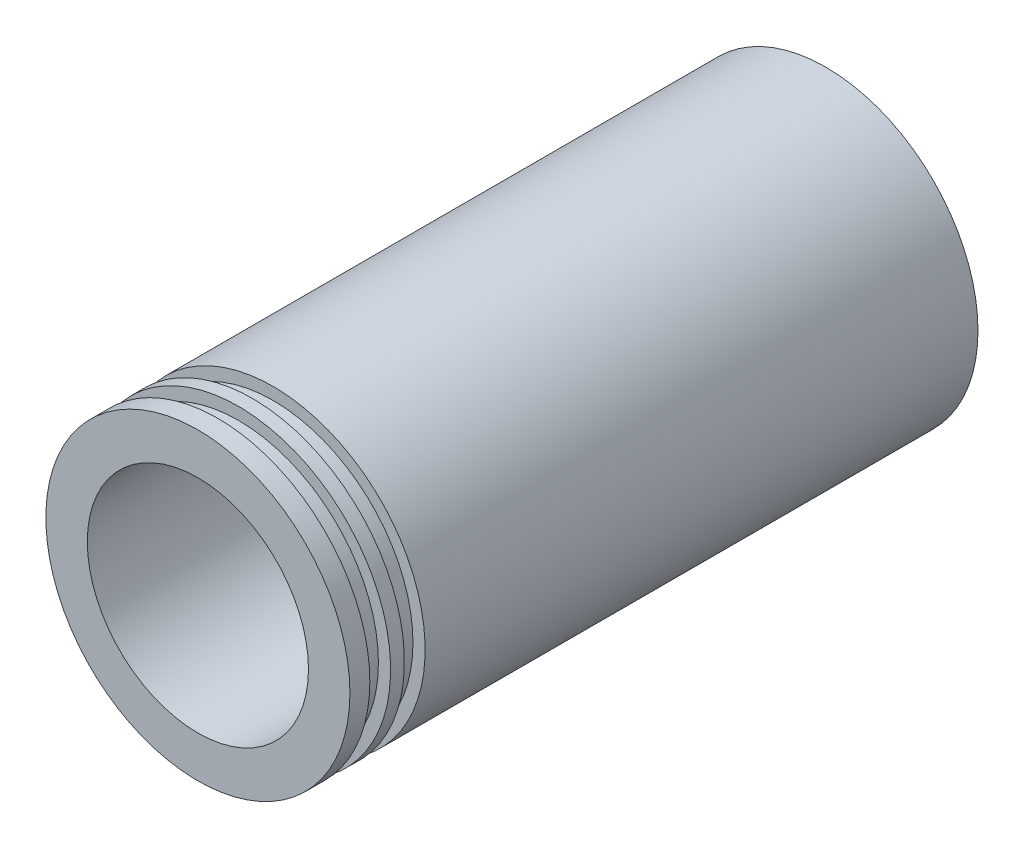
SolidWorks part; units mm, degrees
ref_plane "Front Plane" through (0, 0, 0) normal (0, 0, 1) x (1, 0, 0)
ref_plane "Top Plane" through (0, 0, 0) normal (0, 1, 0) x (1, 0, 0)
ref_plane "Right Plane" through (0, 0, 0) normal (1, 0, 0) x (0, 0, -1)
sketch "Sketch1" plane through (0, 0, 0) normal (0, 0, 1) x (1, 0, 0)
  circle A0 centre (0, 0) radius 34.925
  circle A1 centre (0, 0) radius 25.4
extrude "Boss-Extrude1" add sketch "Sketch1" along normal blind 144.272
sketch "Sketch2" plane through (0, 0, 0) normal (0, 1, 0) x (1, 0, 0)
  line L0 (25.4, 0) -> (-25.4, 0) construction
  circle A0 centre (0, -38.1) radius 5.588
  dimension "D1" = 38.1
extrude "Cut-Extrude1" cut sketch "Sketch2" against normal up to next
sketch "groove" plane through (0, 0, 0) normal (1, 0, 0) x (0, 0, -1)
  line L0 (-139.7, 34.925) -> (-139.7, 32.131)
  line L1 (-139.7, 32.131) -> (-134.9375, 32.131)
  line L2 (-134.9375, 32.131) -> (-134.9375, 34.925)
  line L3 (-134.9375, 34.925) -> (-131.7625, 34.925)
  line L4 (-131.7625, 34.925) -> (-131.7625, 32.131)
  line L5 (-131.7625, 32.131) -> (-127, 32.131)
  line L6 (-127, 32.131) -> (-127, 34.925)
  line L7 (-139.7, 38.1) -> (-127, 38.1)
  line L8 (-127, 38.1) -> (-127, 34.925)
  line L9 (-139.7, 38.1) -> (-139.7, 34.925)
  line L10 (-144.272, 34.925) -> (0, 34.925) construction
  line L11 (0, -34.925) -> (0, 34.925) construction
  dimension "D1" = 2.794
  dimension "D2" = 2.794
  dimension "D3" = 4.7625
  dimension "D4" = 4.7625
  dimension "D5" = 127
  dimension "D6" = 12.7
  dimension "D7" = 3.175
ref_plane "Plane1" through (0, 0, 131.7625) normal (0, 0, 1) x (1, 0, 0)
sketch "groove path" plane through (0, 0, 131.7625) normal (0, 0, 1) x (1, 0, 0)
  circle A0 centre (0, 0) radius 34.925 construction
  circle A1 centre (0, 0) radius 34.925
sweep "Cut-Sweep1" cut profiles "groove" path "groove path"
sketch "Sketch3" plane through (0, 0, 0) normal (1, 0, 0) x (0, 0, -1)
  line L0 (-38.1, 0) -> (-38.1, -34.925) construction
  line L1 (-32.512, -34.925) -> (-38.1, -34.925) construction
  spline S0 degree 2 poles (-43.688, -34.925) (-38.1, -34.0309) (-32.512, -34.925) knots 0 0 0 1 1 1 weights 0.029337 0.034925 0.040513 construction
  point P3 (-38.1, -25.6859)
  point P4 (-38.1, -30.0089)
ref_plane "Plane2" through (0, -34.925, 0) normal (0, 1, 0) x (1, 0, 0)
other "CPoint4" parameters "Diameter"=9.525, "StubLength"=25.4
ref_axis "Axis4" through (0, -44.925, 38.1) along (0, 1, 0)
